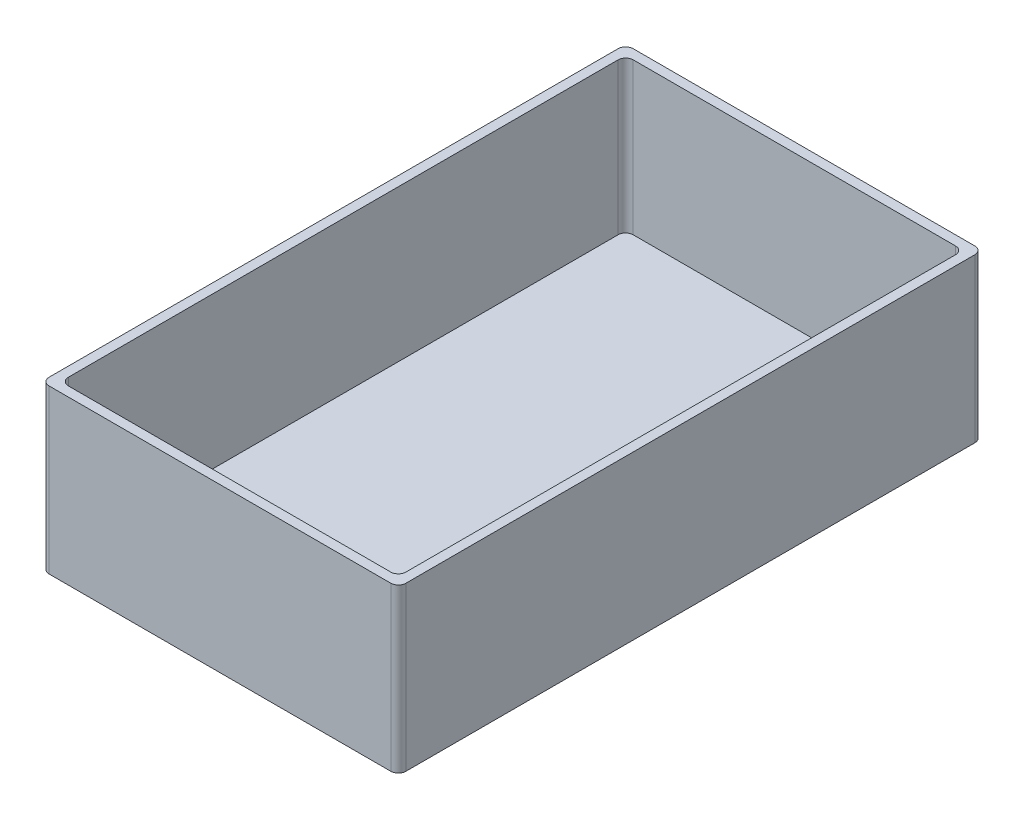
SolidWorks part; units mm, degrees
ref_plane "Front Plane" through (0, 0, 0) normal (0, 0, 1) x (1, 0, 0)
ref_plane "Top Plane" through (0, 0, 0) normal (0, 1, 0) x (1, 0, 0)
ref_plane "Right Plane" through (0, 0, 0) normal (1, 0, 0) x (0, 0, -1)
sketch "Sketch1" plane through (0, 0, 0) normal (0, 1, 0) x (1, 0, 0)
  line L5 (0, 0) -> (47.0912, 0)
  line L6 (0, 0) -> (0, -77.0912)
  line L7 (0, -77.0912) -> (47.0912, -77.0912)
  line L8 (47.0912, 0) -> (47.0912, -77.0912)
extrude "Boss-Extrude1" add sketch "Sketch1" along normal blind 1.5
sketch "Sketch2" plane through (0, 1.5, 0) normal (0, 1, 0) x (1, 0, 0)
  line L3 (1.2728, -1.2728) -> (45.8184, -1.2728)
  line L4 (1.2728, -1.2728) -> (1.2728, -75.8184)
  line L5 (1.2728, -75.8184) -> (45.8184, -75.8184)
  line L6 (45.8184, -1.2728) -> (45.8184, -75.8184)
  line L7 (0, 0) -> (47.0912, 0)
  line L8 (0, 0) -> (0, -77.0912)
  line L9 (0, -77.0912) -> (47.0912, -77.0912)
  line L10 (47.0912, 0) -> (47.0912, -77.0912)
extrude "Boss-Extrude2" add sketch "Sketch2" along normal blind 20
fillet "Fillet4" radius 1 8 edges at (45.8184, 11.5, 1.2728) (1.2728, 11.5, 1.2728) (45.8184, 11.5, 75.8184) (1.2728, 11.5, 75.8184) (47.0912, 10.75, 0) (0, 10.75, 0) (47.0912, 10.75, 77.0912) (0, 10.75, 77.0912)
